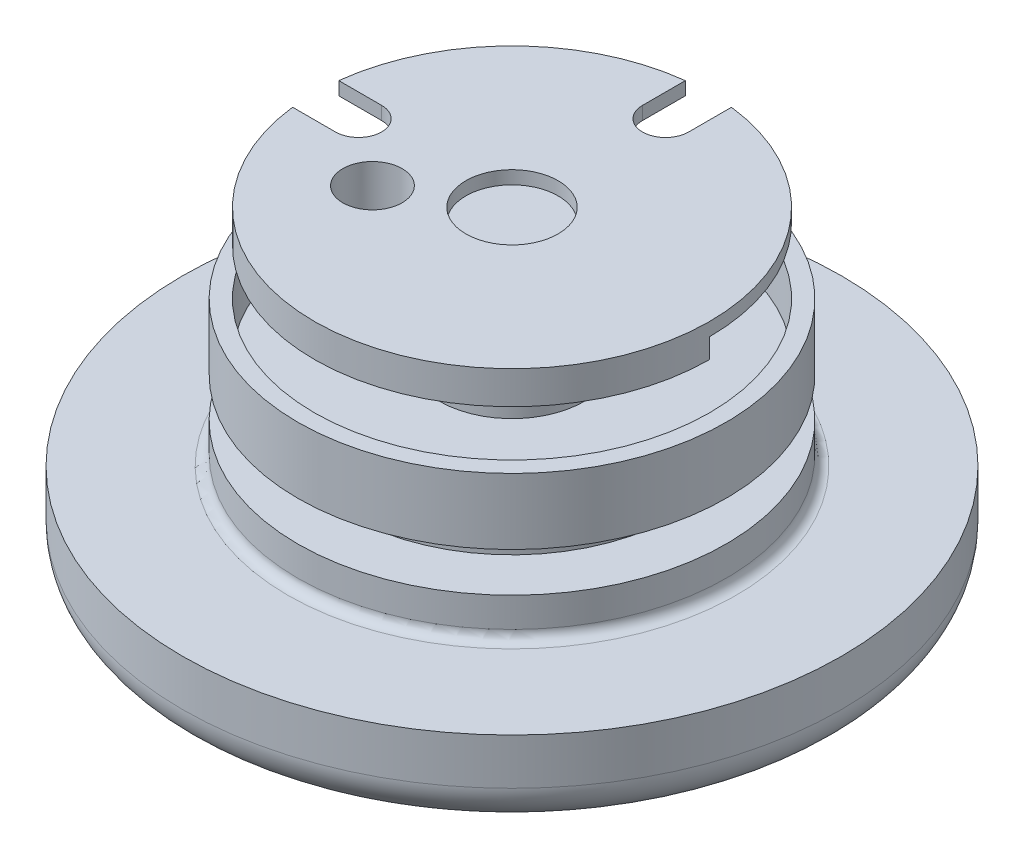
SolidWorks part; units mm, degrees
ref_plane "Planta" through (0, 0, 0) normal (0, 0, 1) x (1, 0, 0)
ref_plane "Alzado" through (0, 0, 0) normal (0, 1, 0) x (1, 0, 0)
ref_plane "Vista lateral" through (0, 0, 0) normal (1, 0, 0) x (0, 0, -1)
sketch "Croquis1" plane through (0, 0, 0) normal (0, 1, 0) x (1, 0, 0)
  circle A0 centre (0, 0) radius 50
  circle A1 centre (0, 0) radius 38.5
  circle A2 centre (0, 0) radius 14
  circle A3 centre (0, 0) radius 11
  dimension "D1" = 100
  dimension "D2" = 77
  dimension "D3" = 28
  dimension "D4" = 22
extrude "Saliente-Extruir1" add sketch "Croquis1" along normal blind 13 contours A0
extrude "Cortar-Extruir1" cut sketch "Croquis1<3>" along normal blind 4 contours A1
sketch "Croquis1<3>" plane through (0, 0, 0) normal (0, 1, 0) x (1, 0, 0) same geometry as "Croquis1"
sketch "Croquis4" plane through (0, 4, 0) normal (0, -1, 0) x (1, 0, 0)
  circle A0 centre (0, 0) radius 11 construction
  circle A1 centre (0, 0) radius 14 construction
  circle A2 centre (0, 0) radius 11
  circle A3 centre (0, 0) radius 14
extrude "Saliente-Extruir3" add sketch "Croquis4" along normal blind 6
extrude "Cortar-Extruir4" cut sketch "Croquis4<2>" against normal through all contours A2
sketch "Croquis4<2>" plane through (0, 4, 0) normal (0, -1, 0) x (1, 0, 0) same geometry as "Croquis4"
fillet "Redondeo1" radius 1.5 1 edges at (0, 4, 38.5)
fillet "Redondeo2" radius 1.5 1 edges at (0, 4, 14)
fillet "Redondeo3" radius 6 1 edges at (0, 0, 50)
sketch "Croquis7" plane through (0, 13, 0) normal (0, 1, 0) x (1, 0, 0)
  circle A0 centre (0, 0) radius 11 construction
  circle A1 centre (0, 0) radius 11
  circle A2 centre (0, 0) radius 32.5
  dimension "D1" = 65
extrude "Saliente-Extruir4" add sketch "Croquis7" along normal blind 6
fillet "Redondeo4" radius 1.5 1 edges at (0, 13, 32.5)
sketch "Croquis9" plane through (0, 19, 0) normal (0, 1, 0) x (1, 0, 0)
  circle A1 centre (0, 0) radius 11 construction
  circle A2 centre (0, 0) radius 25
  circle A3 centre (0, 0) radius 11
  dimension "D2" = 50
extrude "Saliente-Extruir6" add sketch "Croquis9" along normal blind 6
sketch "Croquis10" plane through (0, 25, 0) normal (0, 1, 0) x (1, 0, 0)
  circle A0 centre (0, 0) radius 32.5 construction
  circle A1 centre (0, 0) radius 32.5
  circle A2 centre (0, 0) radius 11 construction
  circle A3 centre (0, 0) radius 11
extrude "Saliente-Extruir7" add sketch "Croquis10" along normal blind 10
sketch "Croquis11" plane through (0, 35, 0) normal (0, 1, 0) x (1, 0, 0)
  circle A0 centre (0, 0) radius 30
  circle A1 centre (0, 0) radius 11 construction
  circle A2 centre (0, 0) radius 11
  dimension "D1" = 60
extrude "Cortar-Extruir5" cut sketch "Croquis11" against normal blind 8
sketch "Croquis12" plane through (0, 27, 0) normal (0, 1, 0) x (1, 0, 0)
  circle A0 centre (0, 0) radius 11 construction
  circle A1 centre (0, 0) radius 11
  circle A2 centre (0, 0) radius 7
  dimension "D1" = 14
extrude "Saliente-Extruir8" add sketch "Croquis12" against normal through all
extrude "Saliente-Extruir9" add sketch "Croquis12<2>" along normal blind 18
sketch "Croquis12<2>" plane through (0, 27, 0) normal (0, 1, 0) x (1, 0, 0) same geometry as "Croquis12"
sketch "Croquis13" plane through (0, -2, 0) normal (0, -1, 0) x (1, 0, 0)
  circle A0 centre (0, 0) radius 11 construction
  circle A1 centre (0, 0) radius 11
extrude "Cortar-Extruir6" cut sketch "Croquis13" against normal blind 10
sketch "Croquis14" plane through (0, 45, 0) normal (0, 1, 0) x (1, 0, 0)
  circle A0 centre (0, 0) radius 7 construction
  circle A1 centre (0, 0) radius 7
  circle A2 centre (0, 0) radius 15
  dimension "D1" = 30
extrude "Saliente-Extruir11" add sketch "Croquis14" against normal blind 10 contours A2
sketch "Croquis17" plane through (0, 45, 0) normal (0, 1, 0) x (1, 0, 0)
  line L0 (30, 0) -> (15, 0)
  line L1 (-15, 0) -> (-30, 0)
  circle A0 centre (0, 0) radius 30 construction
  circle A1 centre (0, 0) radius 30 construction
  circle A2 centre (0, 0) radius 15 construction
  arc A3 (-30, 0) -> (30, 0) centre (0, 0) ccw
  arc A4 (-15, 0) -> (15, 0) centre (0, 0) ccw
extrude "Saliente-Extruir12" add sketch "Croquis17" against normal blind 8
sketch "Croquis18" plane through (0, 0, 0) normal (0, 0, -1) x (-1, 0, 0)
  line L0 (15, 40) -> (30, 42)
  line L1 (15, 37) -> (15, 45) construction
  line L2 (30, 37) -> (30, 45) construction
  line L6 (15, 37) -> (30, 37) construction
  line L7 (30, 42) -> (30, 37)
  line L8 (30, 37) -> (15, 37)
  line L9 (15, 37) -> (15, 40)
  dimension "D1" = 3
ref_axis "Eje1" through (0, 37, 0) along (0, 1, 0)
revolve "Cortar-Revolución1" cut sketch "Croquis18" angle 180 about axis through (0, 37, 0) along (0, 1, 0)
sketch "Croquis19" plane through (0, 45, 0) normal (0, 1, 0) x (1, 0, 0)
  circle A0 centre (0, 0) radius 30 construction
  circle A1 centre (0, 0) radius 30
  circle A2 centre (0, 0) radius 7 construction
  circle A3 centre (0, 0) radius 7
extrude "Saliente-Extruir13" add sketch "Croquis19" along normal blind 2
sketch "Croquis20" plane through (0, 47, 0) normal (0, 1, 0) x (1, 0, 0)
  line L0 (0, 30) -> (0, 0) construction
  line L1 (0, 0) -> (-30, 0) construction
  line L2 (0, 0) -> (-18.0504, -23.9621) construction
  line L3 (3.506, 29.7944) -> (3.506, 23.2944)
  line L4 (-29.7944, 3.506) -> (-23.2944, 3.506)
  line L5 (-3.494, 23.2944) -> (-3.494, 29.7958)
  line L6 (-23.2944, -3.494) -> (-29.7958, -3.494)
  line L7 (0, 0) -> (0.006, 23.2944) construction
  line L8 (0, 0) -> (-23.2944, 0.006) construction
  circle A0 centre (0, 0) radius 30 construction
  circle A1 centre (0, 0) radius 30 construction
  arc A2 (3.506, 29.7944) -> (-3.494, 29.7958) centre (0, 0) ccw
  arc A3 (-3.494, 23.2944) -> (3.506, 23.2944) centre (0.006, 23.2944) ccw
  arc A4 (-30, 0) -> (-29.7958, -3.494) centre (0, 0) ccw
  arc A5 (-23.2944, -3.494) -> (-23.2944, 3.506) centre (-23.2944, 0.006) ccw
  arc A6 (-29.7944, 3.506) -> (-29.7958, -3.494) centre (0, 0) ccw
  point P24 (0, 0)
  dimension "D1" = 7
  dimension "D2" = 3.5
  dimension "D3" = 6.5
  dimension "D5" = 90
  dimension "D4" = 2
extrude "Cortar-Extruir9" cut sketch "Croquis20" against normal blind 10 contours A3 L3 A2 L5 | A6 L4 A5 L6
sketch "Croquis21" plane through (0, 47, 0) normal (0, 1, 0) x (1, 0, 0)
  line L0 (0, 0) -> (-25.9808, -15) construction
  line L1 (0, 0) -> (0, 30) construction
  circle A0 centre (0, 0) radius 30 construction
  circle A1 centre (-13.4234, -7.75) radius 4.5
  dimension "D3" = 9
  dimension "D1" = 120
  dimension "D2" = 15.5
extrude "Cortar-Extruir10" cut sketch "Croquis21" against normal blind 10
